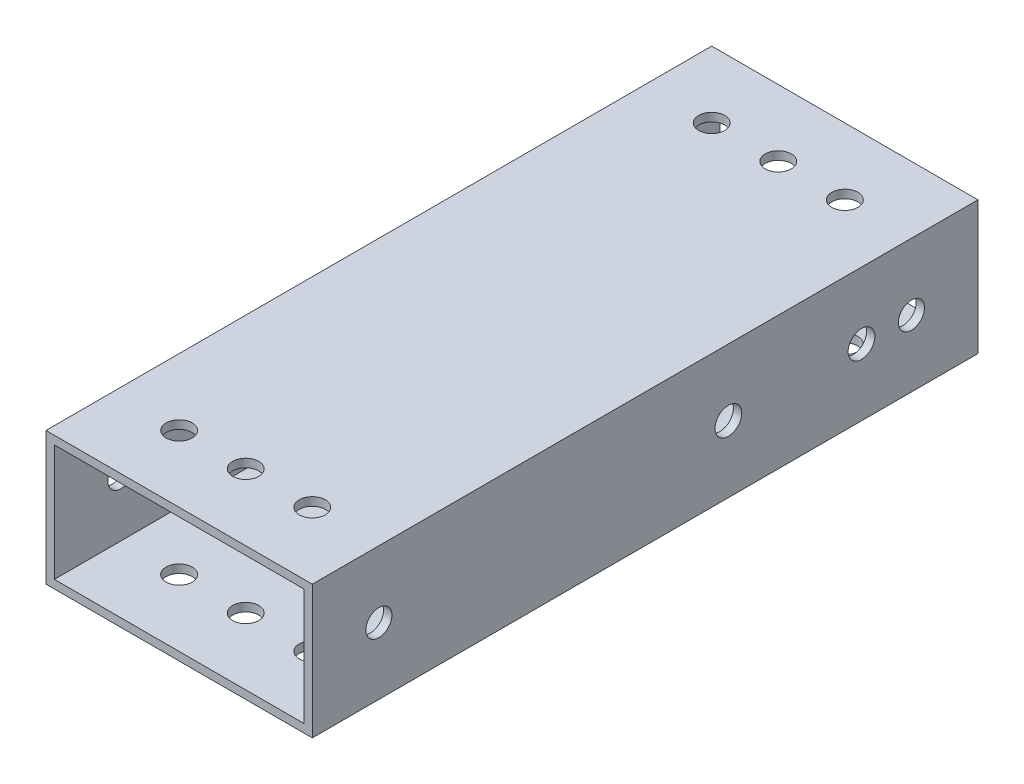
SolidWorks part; units mm, degrees
material "6061-T6 (SS)"
ref_plane "Front Plane" through (0, 0, 0) normal (0, 0, 1) x (1, 0, 0)
ref_plane "Top Plane" through (0, 0, 0) normal (0, 1, 0) x (1, 0, 0)
ref_plane "Right Plane" through (0, 0, 0) normal (1, 0, 0) x (0, 0, -1)
sketch "Sketch1" plane through (0, 0, 0) normal (0, 0, 1) x (1, 0, 0)
  line L0 (-23.8125, 11.1125) -> (23.8125, 11.1125)
  line L1 (-25.4, -12.7) -> (25.4, -12.7)
  line L2 (-25.4, -12.7) -> (-25.4, 12.7)
  line L3 (-25.4, 12.7) -> (25.4, 12.7)
  line L4 (25.4, -12.7) -> (25.4, 12.7)
  line L5 (-25.4, -12.7) -> (25.4, 12.7) construction
  line L6 (-25.4, 12.7) -> (25.4, -12.7) construction
  line L7 (23.8125, -11.1125) -> (23.8125, 11.1125)
  line L8 (-23.8125, -11.1125) -> (23.8125, -11.1125)
  line L9 (-23.8125, -11.1125) -> (-23.8125, 11.1125)
  point P0 (0, 0)
  dimension "D1" = 50.8
  dimension "D2" = 25.4
  dimension "D3" = 1.5875
extrude "Boss-Extrude1" add sketch "Sketch1" along normal mid plane 127
sketch "Sketch2" plane through (0, 12.7, 0) normal (0, 1, 0) x (1, 0, 0)
  line L0 (25.4, 63.5) -> (-25.4, 63.5) construction
  line L1 (25.4, 0) -> (-25.4, 0) construction
  line L2 (25.4, -63.5) -> (25.4, 63.5) construction
  line L3 (-25.4, -63.5) -> (-25.4, 63.5) construction
  circle A0 centre (-12.7, 50.8) radius 2.4892
  circle A1 centre (0, 50.8) radius 2.4892
  circle A2 centre (12.7, 50.8) radius 2.4892
  circle A3 centre (12.7, -50.8) radius 2.4892
  circle A4 centre (0, -50.8) radius 2.4892
  circle A5 centre (-12.7, -50.8) radius 2.4892
  dimension "D4" = 4.9784
  dimension "D1" = 12.7
  dimension "D2" = 12.7
  dimension "D3" = 12.7
extrude "Cut-Extrude1" cut sketch "Sketch2" against normal through all
sketch "Sketch3" plane through (-25.4, 0, 0) normal (-1, 0, 0) x (0, 0, 1)
  line L0 (-63.5, 12.7) -> (-63.5, -12.7) construction
  line L1 (0, 12.7) -> (0, -12.7) construction
  line L2 (63.5, 12.7) -> (-63.5, 12.7) construction
  line L3 (63.5, -12.7) -> (-63.5, -12.7) construction
  circle A0 centre (-50.8, 0) radius 2.4892
  circle A1 centre (50.8, 0) radius 2.4892
  dimension "D1" = 4.9784
  dimension "D2" = 12.7
extrude "Cut-Extrude2" cut sketch "Sketch3" against normal through all contours A1 | A0
sketch "Sketch5" plane through (25.4, 0, 0) normal (1, 0, 0) x (0, 0, -1)
  line L0 (63.5, -12.7) -> (63.5, 12.7) construction
  circle A1 centre (41.275, 0) radius 2.5527
  circle A2 centre (15.875, 0) radius 2.5527
  dimension "D1" = 25.4
  dimension "D3" = 5.1054
  dimension "D4" = 22.225
extrude "Cut-Extrude3" cut sketch "Sketch5" against normal through all
